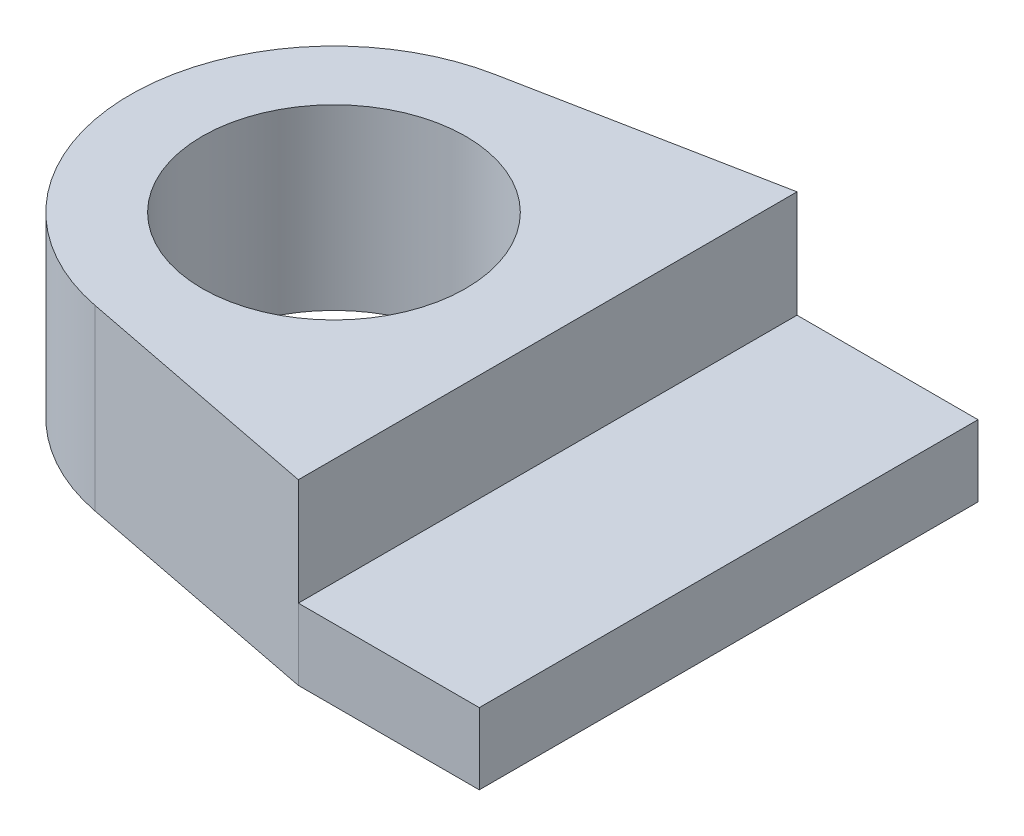
SolidWorks part; units mm, degrees
ref_plane "Front Plane" through (0, 0, 0) normal (0, 0, 1) x (1, 0, 0)
ref_plane "Top Plane" through (0, 0, 0) normal (0, 1, 0) x (1, 0, 0)
ref_plane "Right Plane" through (0, 0, 0) normal (1, 0, 0) x (0, 0, -1)
sketch "Sketch1" plane through (0, 0, 0) normal (0, 1, 0) x (1, 0, 0)
  line L0 (30, -35) -> (30, 35)
  line L1 (0, 0) -> (30, 0) construction
  line L2 (30, 35) -> (-5.4825, 28.0696)
  line L3 (30, -35) -> (-5.4825, -28.0696)
  line L5 (30, 35) -> (55.4, 35)
  line L6 (30, 35) -> (30, -35) construction
  line L7 (30, -35) -> (55.4, -35)
  line L8 (55.4, 35) -> (55.4, -35)
  circle A0 centre (0, 0) radius 18.5
  circle A1 centre (0, 0) radius 28.6 construction
  arc A2 (-5.4825, 28.0696) -> (-5.4825, -28.0696) centre (0, 0) ccw
  point P7 (30, 0)
  dimension "D1" = 37
  dimension "D2" = 57.2
  dimension "D3" = 30
  dimension "D4" = 70
  dimension "D5" = 25.4
extrude "Boss-Extrude2" add sketch "Sketch1" along normal blind 15 contours L2 A2 L3 L0 A0 region at (12.4337, 0, 30.6388)
extrude "Boss-Extrude3" add sketch "Sketch1<3>" against normal blind 10 contours L2 A2 L3 L0 A0 | L8 L5 L0 L7 region at (12.4337, 0, 30.6388) region at (42.7, 0, 0)
sketch "Sketch1<3>" plane through (0, 0, 0) normal (0, 1, 0) x (1, 0, 0) same geometry as "Sketch1"
